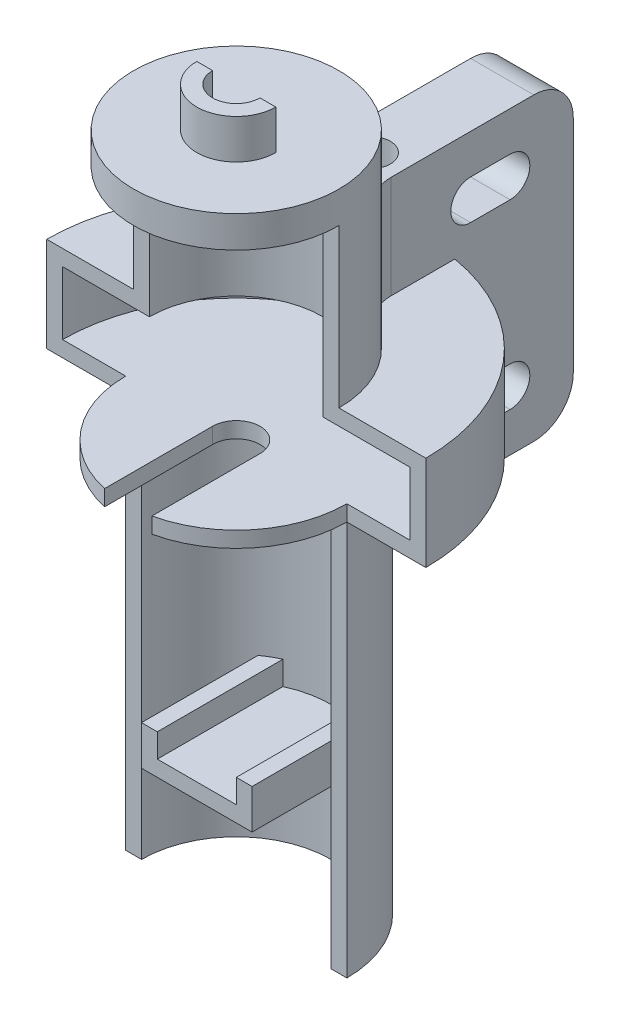
SolidWorks part; units mm, degrees
ref_plane "Front Plane" through (0, 0, 0) normal (0, 0, 1) x (1, 0, 0)
ref_plane "Top Plane" through (0, 0, 0) normal (0, 1, 0) x (1, 0, 0)
ref_plane "Right Plane" through (0, 0, 0) normal (1, 0, 0) x (0, 0, -1)
sketch "Sketch1" plane through (0, 0, 0) normal (0, 1, 0) x (1, 0, 0)
  line L0 (3, 0) -> (3, -13.6748)
  line L1 (-3, 0) -> (-3, -13.6748)
  line L2 (-14, 0) -> (-24, 0)
  line L3 (14, 0) -> (24, 0)
  circle A0 centre (0, 0) radius 14
  circle A1 centre (0, 0) radius 3
  arc A2 (24, 0) -> (-24, 0) centre (0, 0) ccw
  arc A3 (14, 0) -> (-14, 0) centre (0, 0) ccw
  dimension "D1" = 28
  dimension "D2" = 6
  dimension "D3" = 10
extrude "Motor-frontplate" add sketch "Sketch1" along normal blind 2 contours A1 L0 A0 L1 | L3 A2 L2 A3 region at (0, 0, -3.3937)
sketch "Sketch2" plane through (0, 0, 0) normal (0, -1, 0) x (1, 0, 0)
  line L2 (-12, 0) -> (-14, 0)
  line L3 (12, 0) -> (14, 0)
  arc A1 (-14, 0) -> (14, 0) centre (0, 0) ccw
  arc A3 (14, 0) -> (3, 13.6748) centre (0, 0) ccw construction
  arc A4 (-12, 0) -> (12, 0) centre (0, 0) ccw
  dimension "D1" = 2
extrude "Motorkrybbe" add sketch "Sketch2" along normal blind 50 contours A4 L3 A1 L2
sketch "Sketch5" plane through (0, 2, 0) normal (0, 1, 0) x (1, 0, 0)
  line L0 (-24, 0) -> (-22, 0)
  line L1 (24, 0) -> (22, 0)
  arc A1 (24, 0) -> (-24, 0) centre (0, 0) ccw construction
  arc A2 (22, 0) -> (-22, 0) centre (0, 0) ccw
  arc A3 (22, 0) -> (-22, 0) centre (0, 0) ccw
  arc A4 (24, 0) -> (-24, 0) centre (0, 0) ccw
  dimension "D1" = 2
extrude "Skygge - Kappe" add sketch "Sketch5" along normal blind 8 contours A3 L0 A4 L1
sketch "Sketch6" plane through (0, 10, 0) normal (0, 1, 0) x (1, 0, 0)
  line L0 (-24, 0) -> (-11, 0)
  line L1 (11, 0) -> (24, 0)
  arc A0 (-11, 0) -> (11, 0) centre (0, 0) cw
  arc A1 (24, 0) -> (-24, 0) centre (0, 0) ccw construction
  arc A2 (24, 0) -> (-24, 0) centre (0, 0) ccw
  dimension "D1" = 11
extrude "Skygge - Topp" add sketch "Sketch6" along normal blind 2
sketch "Sketch7" plane through (0, 12, 0) normal (0, 1, 0) x (1, 0, 0)
  line L0 (-4, 12.3693) -> (-4, 23.6643)
  line L1 (4, 23.6643) -> (4, 12.3693)
  arc A0 (24, 0) -> (-24, 0) centre (0, 0) ccw construction
  arc A1 (11, 0) -> (-11, 0) centre (0, 0) ccw construction
  arc A2 (24, 0) -> (-24, 0) centre (0, 0) ccw
  arc A3 (11, 0) -> (-11, 0) centre (0, 0) ccw
  arc A4 (4, 12.3693) -> (-4, 12.3693) centre (0, 0) ccw
  arc A5 (4, 23.6643) -> (-4, 23.6643) centre (0, 0) ccw
  dimension "D3" = 2
  dimension "D1" = 4
  dimension "D2" = 4
extrude "LEDholder - Topp" add sketch "Sketch7" along normal blind 13 contours L1 A4 L0 A5
sketch "Sketch8" plane through (0, 0, 0) normal (0, -1, 0) x (1, 0, 0)
  line L0 (4, -23.6643) -> (4, -13.4164)
  line L1 (4, -23.6643) -> (4, -12.3693) construction
  line L2 (-4, -23.6643) -> (-4, -13.4164)
  line L3 (-4, -12.3693) -> (-4, -23.6643) construction
  arc A0 (-14, 0) -> (14, 0) centre (0, 0) ccw construction
  arc A1 (4, -13.4164) -> (-4.105, -13.3846) centre (0, 0) cw
  arc A2 (4, -23.6643) -> (-4, -23.6643) centre (0, 0) cw
  arc M1 (14, 0) -> (-14, 0) centre (0, 0) cw
  arc M3 (-24, 0) -> (24, 0) centre (0, 0) ccw
extrude "LEDholder - Bunn" add sketch "Sketch8" along normal blind 13 contours L2 L0 M3 M1 region at (0, 0, -18.8468)
sketch "Sketch10" plane through (0, -13, 0) normal (0, -1, 0) x (1, 0, 0)
  line L2 (0, 0) -> (0, -14)
  line L3 (0, -14) -> (0, -14.5)
  line L4 (0, -14.5) -> (0, -17)
  arc A0 (-4, -13.4164) -> (4, -13.4164) centre (0, 0) ccw construction
  arc A1 (-4, -13.4164) -> (4, -13.4164) centre (0, 0) ccw
  circle A3 centre (0, -17) radius 2.5
  dimension "D1" = 5
  dimension "D2" = 0.5
extrude "LEDhull" cut sketch "Sketch10" against normal through all contours A3 region at (-1.7178, -13, -18.7178)
sketch "Sketch11" plane through (0, 12, 0) normal (0, 1, 0) x (1, 0, 0)
  line L0 (-24, 0) -> (-11, 0) construction
  line L1 (11, 0) -> (24, 0) construction
  line L2 (-13, 0) -> (-11, 0)
  line L3 (13, 0) -> (11, 0)
  arc A0 (-11, 0) -> (11, 0) centre (0, 0) cw
  arc A1 (11, 0) -> (-11, 0) centre (0, 0) ccw construction
  arc A2 (-13, 0) -> (13, 0) centre (0, 0) cw
  dimension "D1" = 2
extrude "Rotorkappe - Vegg" add sketch "Sketch11" along normal blind 20
sketch "Sketch12" plane through (0, 32, 0) normal (0, 1, 0) x (1, 0, 0)
  circle A0 centre (0, 0) radius 13
extrude "Laserholder" add sketch "Sketch12" along normal blind 4
hole_wizard "Laser - hull" positions "Sketch13" profile "Sketch15" hole size "Ø6.0" standard "ISO" end condition up to next
sketch "Sketch13" plane through (0, 36, 0) normal (0, 1, 0) x (1, 0, 0)
  point P0 (0, 0)
sketch "Sketch15" plane through (0, 36, 0) normal (1, 0, 0) x (0, 0, 1)
  line L0 (0, 0) -> (0, 4)
  line L1 (0, 4) -> (3, 4)
  line L2 (3, 4) -> (3, 0)
  line L5 (3, 0) -> (0, 0)
  line L11 (0, -6.35) -> (0, 107.95) construction
  dimension "Thru Hole Dia." = 6
  dimension "Thru Hole Depth" = 4
sketch "Sketch19" plane through (0, 0, 0) normal (0, 0, 1) x (1, 0, 0)
  line L0 (0, -33) -> (-5, -33)
  line L9 (-5, -33) -> (-5, -30)
  line L10 (-5, -30) -> (-7, -30)
  line L11 (-7, -30) -> (-7, -35)
  line L12 (-7, -35) -> (0, -35)
  line L13 (0, -35) -> (0, -33)
  line L14 (0, 0) -> (0, -33) construction
  dimension "D1" = 30
  dimension "D2" = 2
  dimension "D3" = 3
  dimension "D4" = 2
  dimension "D5" = 5
extrude "Boss-Extrude12" add sketch "Sketch19" along normal blind 5 and the other way up to next
mirror "Mirror2" about plane through (0, -35, -24.002) normal (1, 0, 0) of "Boss-Extrude12"
sketch "Sketch20" plane through (0, 25, 0) normal (0, 1, 0) x (1, 0, 0)
  line L0 (4, 23.6643) -> (4, 38.6643)
  line L1 (4, 38.6643) -> (-4, 38.6643)
  line L2 (-4, 38.6643) -> (-4, 23.6643)
  arc A0 (4, 23.6643) -> (-4, 23.6643) centre (0, 0) ccw construction
  arc A1 (4, 23.6643) -> (-4, 23.6643) centre (0, 0) ccw
  dimension "D1" = 15
extrude "LED - kabelholder" add sketch "Sketch20" against normal blind 38
sketch "Sketch21" plane through (4, 0, 0) normal (1, 0, 0) x (0, 0, -1)
  line L0 (25.6643, 17.5) -> (30.6643, 17.5) construction
  line L1 (25.6643, 20) -> (30.6643, 20)
  line L2 (25.6643, 15) -> (30.6643, 15)
  line L3 (38.6643, -13) -> (38.6643, 25) construction
  line L4 (12.3693, 25) -> (38.6643, -13) construction
  line L5 (38.6643, 25) -> (12.3693, 25) construction
  line L6 (25.5168, 6) -> (38.6643, 6)
  line L7 (25.6643, -5.5) -> (30.6643, -5.5) construction
  line L8 (25.6643, -8) -> (30.6643, -8)
  line L9 (25.6643, -3) -> (30.6643, -3)
  arc A0 (25.6643, 20) -> (25.6643, 15) centre (25.6643, 17.5) ccw
  arc A1 (30.6643, 15) -> (30.6643, 20) centre (30.6643, 17.5) ccw
  arc A2 (25.6643, -8) -> (25.6643, -3) centre (25.6643, -5.5) cw
  arc A3 (30.6643, -3) -> (30.6643, -8) centre (30.6643, -5.5) cw
  point P2 (28.1643, 17.5)
  point P19 (28.1643, -5.5)
  dimension "D1" = 8
  dimension "D2" = 5
  dimension "D3" = 5
  dimension "D4" = 5
extrude "Kabelholder - hull" cut sketch "Sketch21" against normal up to next contours L2 A1 L1 A0 | A3 L9 A2 L8 region at (4, 17.5, -28.1643) region at (4, -5.5, -28.1643)
fillet "Fillet1" radius 5 2 edges at (0, -13, -38.6643) (0, 25, -38.6643)
sketch "Sketch22" plane through (0, 36, 0) normal (0, 1, 0) x (1, 0, 0)
  line L0 (-3, 0) -> (-5, 0)
  line L1 (3, 0) -> (5, 0)
  circle A1 centre (0, 0) radius 3 construction
  arc A2 (3, 0) -> (-3, 0) centre (0, 0) cw
  arc A3 (5, 0) -> (-5, 0) centre (0, 0) cw
  dimension "D1" = 2
extrude "Boss-Extrude14" add sketch "Sketch22" along normal blind 5
fillet "Fillet3" radius 5 4 edges at (-4, -6.5, -13.4164) (-4, 18.5, -12.3693) (4, -6.5, -13.4164) (4, 18.5, -12.3693)
